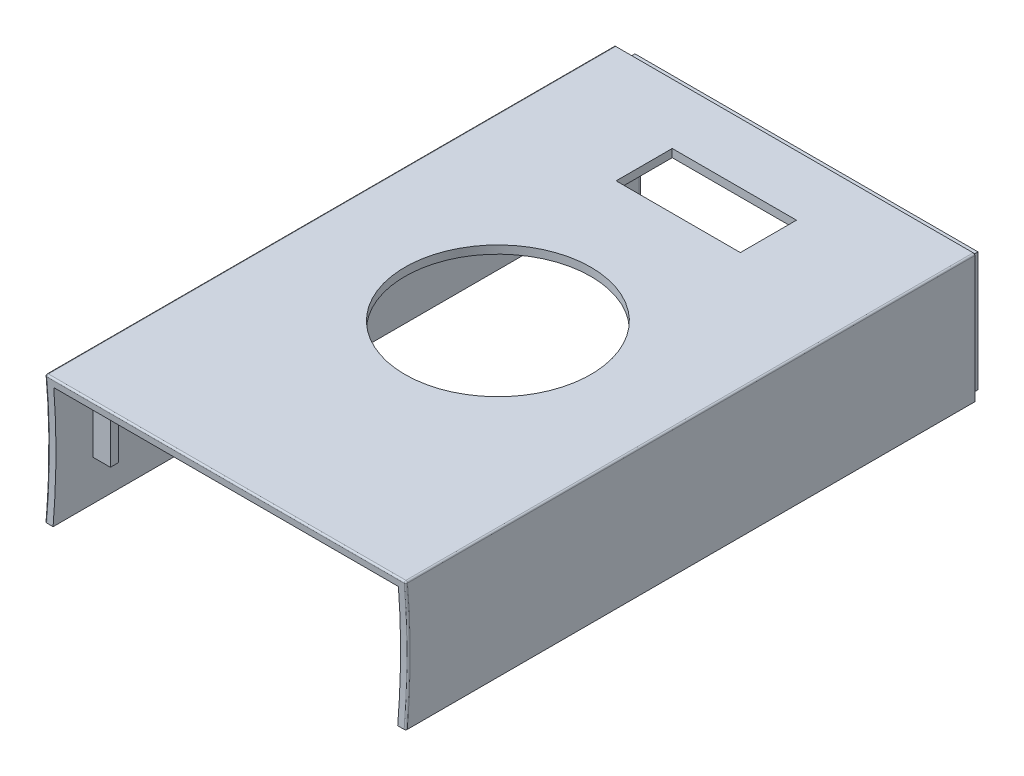
SolidWorks part; units mm, degrees
ref_plane "Front Plane" through (0, 0, 0) normal (0, 0, 1) x (1, 0, 0)
ref_plane "Top Plane" through (0, 0, 0) normal (0, 1, 0) x (1, 0, 0)
ref_plane "Right Plane" through (0, 0, 0) normal (1, 0, 0) x (0, 0, -1)
sketch "Sketch1" plane through (0, 0, 0) normal (0, 0, 1) x (1, 0, 0)
  line L1 (0, 0) -> (90, 0)
  line L2 (0, 0) -> (0, 32)
  line L3 (0, 32) -> (90, 32)
  line L4 (90, 0) -> (90, 32)
  dimension "D1" = 32
  dimension "D2" = 90
extrude "Boss-Extrude1" add sketch "Sketch1" along normal blind 142
sketch "Sketch2" plane through (0, 0, 0) normal (0, -1, 0) x (1, 0, 0)
  line L1 (0, 142) -> (90, 142) construction
  line L5 (2, 142) -> (2, 0)
  line L6 (0, 0) -> (90, 0) construction
  line L7 (2, 0) -> (88, 0)
  line L8 (88, 0) -> (88, 142)
  line L13 (88, 142) -> (2, 142)
  line L14 (45, 104.4498) -> (45, -4.9587) construction
  line L15 (90, 142) -> (90, 0) construction
  line L16 (0, 142) -> (0, 0) construction
  point P18 (45, 0)
  point P19 (45, 142)
  dimension "D1" = 2
extrude "Cut-Extrude1" cut sketch "Sketch2" against normal offset from surface (30 mm away) 2 up to face at (45, 32, 71)
sketch "Sketch3" plane through (0, 32, 0) normal (0, 1, 0) x (1, 0, 0)
  line L0 (45, 0) -> (45, -104.8315) construction
  line L1 (90, 0) -> (0, 0) construction
  line L3 (29.5, -15) -> (60.5, -15)
  line L4 (29.5, -15) -> (29.5, -29)
  line L5 (29.5, -29) -> (60.5, -29)
  line L6 (60.5, -15) -> (60.5, -29)
  circle A0 centre (45, -74) radius 23.2
  dimension "D1" = 46.4
  dimension "D2" = 74
  dimension "D3" = 31
  dimension "D4" = 14
  dimension "D5" = 15
extrude "Cut-Extrude2" cut sketch "Sketch3" against normal through all
sketch "Sketch4" plane through (0, 30, 0) normal (0, -1, 0) x (1, 0, 0)
  line L0 (45, 0) -> (45, 145.6541) construction
  line L1 (88, 0) -> (2, 0) construction
  line L2 (2, 0) -> (2, 142) construction
  line L3 (2, 132) -> (6.3, 132)
  line L4 (2, 132) -> (2, 130)
  line L5 (2, 130) -> (6.3, 130)
  line L6 (6.3, 132) -> (6.3, 130)
  line L7 (2, 142) -> (88, 142) construction
  line L8 (88, 130) -> (83.7, 130)
  line L9 (83.7, 132) -> (83.7, 130)
  line L10 (88, 132) -> (83.7, 132)
  line L11 (88, 132) -> (88, 130)
  dimension "D1" = 10
  dimension "D2" = 2
  dimension "D3" = 4.3
extrude "Boss-Extrude2" add sketch "Sketch4" along normal blind 20
sketch "Sketch7" plane through (0, 0, 0) normal (0, 0, -1) x (-1, 0, 0)
  line L0 (-88, 30) -> (-88, 0) construction
  line L1 (-2, 30) -> (-2, 0) construction
  line L2 (-88, 30) -> (-2, 30) construction
  line L3 (-88, 30) -> (-88, 0)
  line L4 (-2, 30) -> (-2, 0)
  line L5 (-88, 30) -> (-2, 30)
  line L6 (-88, 0) -> (-87.8, 0)
  line L7 (-87.8, 0) -> (-87.8, 29.8)
  line L8 (-87.8, 29.8) -> (-2.2, 29.8)
  line L9 (-2.2, 29.8) -> (-2.2, 0)
  line L10 (-2.2, 0) -> (-2, 0)
  dimension "D1" = 0.2
  dimension "D2" = 0.2
  dimension "D3" = 0.2
extrude "Boss-Extrude5" add sketch "Sketch7" against normal blind 3
sketch "Sketch8" plane through (0, 0, 0) normal (0, 0, -1) x (-1, 0, 0)
  line L0 (-2.2, 29.8) -> (-2.2, 0) construction
  line L1 (-87.8, 29.8) -> (-2.2, 29.8) construction
  line L2 (-87.8, 0) -> (-87.8, 29.8) construction
  line L3 (-2.2, 29.8) -> (-2.2, 0)
  line L4 (-87.8, 29.8) -> (-2.2, 29.8)
  line L5 (-87.8, 0) -> (-87.8, 29.8)
  line L6 (-87.8, 0) -> (-85.8, 0)
  line L7 (-85.8, 0) -> (-85.8, 27.8)
  line L8 (-85.8, 27.8) -> (-4.2, 27.8)
  line L9 (-4.2, 27.8) -> (-4.2, 0)
  line L10 (-4.2, 0) -> (-2.2, 0)
  line L11 (0, 0) -> (-2.2, 0) construction
  dimension "D1" = 2
  dimension "D2" = 2
  dimension "D3" = 2
extrude "Boss-Extrude6" add sketch "Sketch8" along normal mid plane 6
sketch "Sketch10" plane through (90, 0, 0) normal (1, 0, 0) x (0, 0, -1)
  line L0 (-142, 0) -> (-142, 32) construction
  line L1 (-142, 0) -> (0, 0) construction
  line L2 (-142, 32) -> (-142, 0)
  arc A0 (-142, 32) -> (-142, 0) centre (-321.2875, 16) cw
  dimension "D1" = 180
extrude "Cut-Extrude3" cut sketch "Sketch10" against normal up to surface (90 mm away) up to face at (0, 16, 71)
fillet "Fillet1" radius 0.4 5 edges at (90, 32, 71) (0, 32, 71) (90, 16, 141.2875) (0, 16, 141.2875) (45, 32, 142)
fillet "Fillet3" radius 1 9 edges at (85.8, 13.9, -3) (4.2, 13.9, -3) (45, 27.8, -3) (4.2, 13.9, 3) (2, 15, 3) (45, 27.8, 3) (45, 30, 3) (88, 15, 3) (85.8, 13.9, 3)
